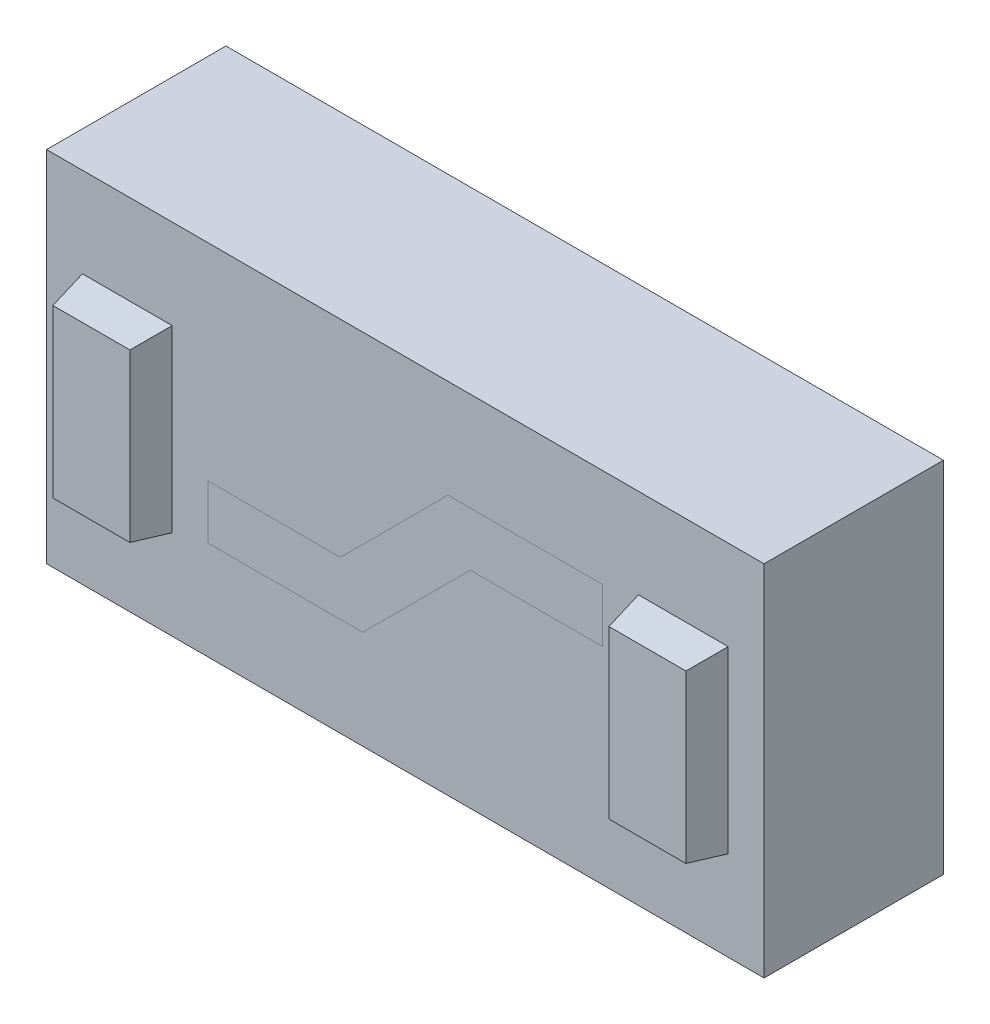
SolidWorks part; units mm, degrees
other "graphite_pad_2"
other "graphite_pad"
other "blue_inlay"
other "white_box"
ref_plane "Front Plane" through (0, 0, 0) normal (0, 0, 1) x (1, 0, 0)
ref_plane "Top Plane" through (0, 0, 0) normal (0, 1, 0) x (1, 0, 0)
ref_plane "Right Plane" through (0, 0, 0) normal (1, 0, 0) x (0, 0, -1)
sketch "Sketch1" plane through (0, 0, 0) normal (0, 0, 1) x (1, 0, 0)
  line L1 (-20, -10) -> (20, -10)
  line L2 (-20, -10) -> (-20, 10)
  line L3 (-20, 10) -> (20, 10)
  line L4 (20, -10) -> (20, 10)
  line L5 (-20, -10) -> (20, 10) construction
  line L6 (-20, 10) -> (20, -10) construction
  point P0 (0, 0)
extrude "Boss-Extrude1" add sketch "Sketch1" along normal blind 10
sketch "Sketch2" plane through (0, 0, 10) normal (0, 0, 1) x (1, 0, 0)
  line L0 (-3.6213, -1.5) -> (2.3787, 4.5)
  line L1 (2.3787, 4.5) -> (11, 4.5)
  line L2 (11, 4.5) -> (11, 1.5)
  line L3 (11, 1.5) -> (3.6213, 1.5)
  line L4 (3.6213, 1.5) -> (-2.3787, -4.5)
  line L5 (-2.3787, -4.5) -> (-11, -4.5)
  line L6 (-11, -4.5) -> (-11, -1.5)
  line L7 (-11, -1.5) -> (-3.6213, -1.5)
extrude "Cut-Extrude1" cut sketch "Sketch2" against normal blind 1.2
extrude "Boss-Extrude2" add sketch "Sketch2<2>" against normal blind 1.2 separate body
sketch "Sketch2<2>" plane through (0, 0, 10) normal (0, 0, 1) x (1, 0, 0) same geometry as "Sketch2"
sketch "Sketch3" plane through (0, 0, 10) normal (0, 0, 1) x (1, 0, 0)
  line L1 (-18, -5) -> (-13, -5)
  line L2 (-18, -5) -> (-18, 5)
  line L3 (-18, 5) -> (-13, 5)
  line L4 (-13, -5) -> (-13, 5)
  line L5 (-18, -5) -> (-13, 5) construction
  line L6 (-18, 5) -> (-13, -5) construction
  line L7 (13, -5) -> (18, -5)
  line L8 (13, -5) -> (13, 5)
  line L9 (13, 5) -> (18, 5)
  line L10 (18, -5) -> (18, 5)
  line L11 (13, -5) -> (18, 5) construction
  line L12 (13, 5) -> (18, -5) construction
  point P0 (-15.5, 0)
  point P5 (15.5, 0)
extrude "Boss-Extrude3" add sketch "Sketch3" along normal blind 2 draft 10 separate body
